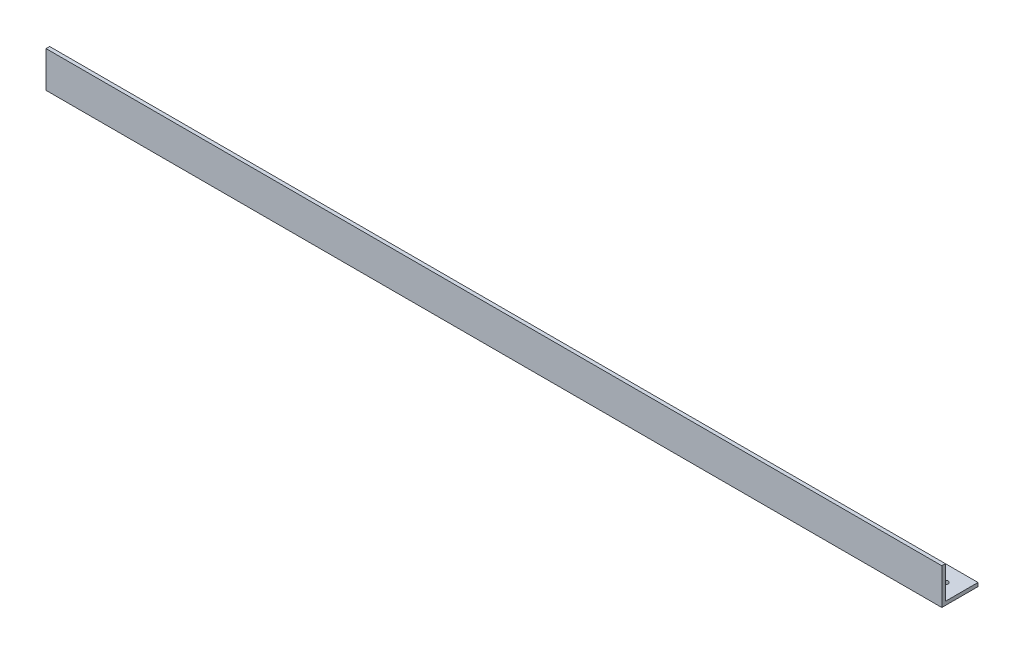
SolidWorks part; units mm, degrees
ref_plane "Front Plane" through (0, 0, 0) normal (0, 0, 1) x (1, 0, 0)
ref_plane "Top Plane" through (0, 0, 0) normal (0, 1, 0) x (1, 0, 0)
ref_plane "Right Plane" through (0, 0, 0) normal (1, 0, 0) x (0, 0, -1)
sketch "Sketch1" plane through (0, 0, 0) normal (1, 0, 0) x (0, 0, -1)
  line L0 (0, 20) -> (0, 0)
  line L1 (0, 0) -> (20, 0)
  line L2 (20, 0) -> (20, 2)
  line L3 (20, 2) -> (2, 2)
  line L4 (2, 2) -> (2, 20)
  line L5 (2, 20) -> (0, 20)
  dimension "D1" = 20
  dimension "D2" = 20
  dimension "D3" = 2
  dimension "D4" = 2
extrude "Boss-Extrude1" add sketch "Sketch1" along normal blind 325 and the other way blind 170
sketch "Sketch2" plane through (0, 2, 0) normal (0, 1, 0) x (1, 0, 0)
  line L0 (-170, 0) -> (325, 0) construction
  line L1 (325, 20) -> (325, 2) construction
  line L2 (-170, 20) -> (325, 20) construction
  line L3 (-170, 20) -> (-170, 2) construction
  circle A0 centre (0, 12.5) radius 2.5
  circle A1 centre (316, 11) radius 1.5
  circle A2 centre (-161, 11) radius 1.5
  dimension "D2" = 5
  dimension "D5" = 3
  dimension "D8" = 3
  dimension "D1" = 12.5
  dimension "D3" = 9
  dimension "D4" = 9
  dimension "D6" = 9
  dimension "D7" = 9
extrude "Cut-Extrude1" cut sketch "Sketch2" against normal blind 2
